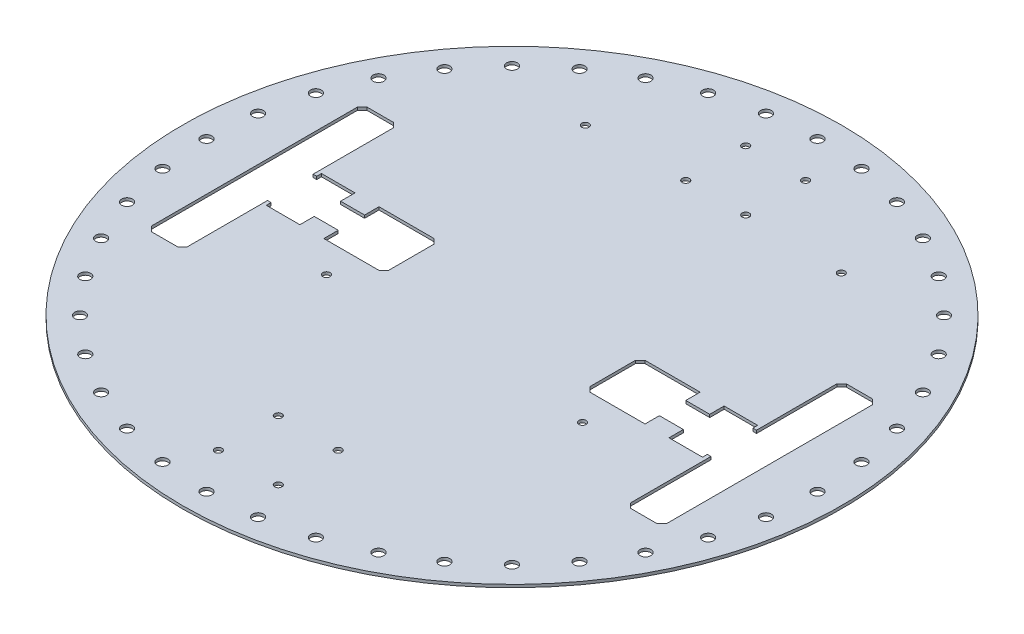
SolidWorks part; units mm, degrees
ref_plane "Front Plane" through (0, 0, 0) normal (0, 0, 1) x (1, 0, 0)
ref_plane "Top Plane" through (0, 0, 0) normal (0, 1, 0) x (1, 0, 0)
ref_plane "Right Plane" through (0, 0, 0) normal (1, 0, 0) x (0, 0, -1)
sketch "Sketch1" plane through (0, 0, 0) normal (0, 1, 0) x (1, 0, 0)
  circle A0 centre (0, 0) radius 137.5
  dimension "D1" = 275
extrude "Boss-Extrude1" add sketch "Sketch1" along normal blind 1.2
sketch "Sketch3" plane through (0, 1.2, 0) normal (0, 1, 0) x (1, 0, 0)
  line L0 (0, 127.4549) -> (0, 0) construction
  line L1 (0, 0) -> (19.9383, 125.8858) construction
  line L2 (39.3857, 121.2169) -> (0, 0) construction
  circle A0 centre (0, 127.4549) radius 2.25
  circle A2 centre (19.9383, 125.8858) radius 2.25
  circle A3 centre (39.3857, 121.2169) radius 2.25
  circle A4 centre (57.8633, 113.5632) radius 2.25
  circle A5 centre (74.9161, 103.1132) radius 2.25
  circle A6 centre (90.1243, 90.1243) radius 2.25
  circle A7 centre (103.1132, 74.9161) radius 2.25
  circle A8 centre (113.5632, 57.8633) radius 2.25
  circle A9 centre (121.2169, 39.3857) radius 2.25
  circle A10 centre (125.8858, 19.9383) radius 2.25
  circle A11 centre (127.4549, 0) radius 2.25
  circle A12 centre (125.8858, -19.9383) radius 2.25
  circle A13 centre (121.2169, -39.3857) radius 2.25
  circle A14 centre (113.5632, -57.8633) radius 2.25
  circle A15 centre (103.1132, -74.9161) radius 2.25
  circle A16 centre (90.1243, -90.1243) radius 2.25
  circle A17 centre (74.9161, -103.1132) radius 2.25
  circle A18 centre (57.8633, -113.5632) radius 2.25
  circle A19 centre (39.3857, -121.2169) radius 2.25
  circle A20 centre (19.9383, -125.8858) radius 2.25
  circle A21 centre (0, -127.4549) radius 2.25
  circle A22 centre (-19.9383, -125.8858) radius 2.25
  circle A23 centre (-39.3857, -121.2169) radius 2.25
  circle A24 centre (-57.8633, -113.5632) radius 2.25
  circle A25 centre (-74.9161, -103.1132) radius 2.25
  circle A26 centre (-90.1243, -90.1243) radius 2.25
  circle A27 centre (-103.1132, -74.9161) radius 2.25
  circle A28 centre (-113.5632, -57.8633) radius 2.25
  circle A29 centre (-121.2169, -39.3857) radius 2.25
  circle A30 centre (-125.8858, -19.9383) radius 2.25
  circle A31 centre (-127.4549, 0) radius 2.25
  circle A32 centre (-125.8858, 19.9383) radius 2.25
  circle A33 centre (-121.2169, 39.3857) radius 2.25
  circle A34 centre (-113.5632, 57.8633) radius 2.25
  circle A35 centre (-103.1132, 74.9161) radius 2.25
  circle A36 centre (-90.1243, 90.1243) radius 2.25
  circle A37 centre (-74.9161, 103.1132) radius 2.25
  circle A38 centre (-57.8633, 113.5632) radius 2.25
  circle A39 centre (-39.3857, 121.2169) radius 2.25
  circle A40 centre (-19.9383, 125.8858) radius 2.25
  dimension "D1" = 4.5
  dimension "D2" = 40
  dimension "D3" = 20
extrude "Cut-Extrude1" cut sketch "Sketch3" against normal through all
sketch "Sketch4" plane through (0, 1.2, 0) normal (0, 1, 0) x (1, 0, 0)
  line L0 (0, 137.5) -> (0, -137.5) construction
  line L1 (-137.5, 0) -> (137.5, 0) construction
  line L2 (-107.5, -43) -> (-107.5, 43)
  line L3 (-105.5, 45) -> (-94.5, 45)
  line L4 (-92.5, 43) -> (-92.5, 9.5)
  line L5 (-92.5, 9.5) -> (-91, 9.5)
  line L6 (-91, 9.5) -> (-91, 11.5)
  line L7 (-91, 11.5) -> (-77, 11.5)
  line L8 (-77, 11.5) -> (-77, 5.5)
  line L9 (-77, 5.5) -> (-67, 5.5)
  line L10 (-67, 5.5) -> (-67, 11.5)
  line L11 (-67, 11.5) -> (-44, 11.5)
  line L12 (-42, 9.5) -> (-42, -9.5)
  line L13 (-67, -11.5) -> (-44, -11.5)
  line L14 (-67, -5.5) -> (-67, -11.5)
  line L15 (-77, -5.5) -> (-67, -5.5)
  line L16 (-77, -11.5) -> (-77, -5.5)
  line L17 (-91, -11.5) -> (-77, -11.5)
  line L18 (-91, -9.5) -> (-91, -11.5)
  line L19 (-92.5, -9.5) -> (-91, -9.5)
  line L20 (-92.5, -43) -> (-92.5, -9.5)
  line L21 (-105.5, -45) -> (-94.5, -45)
  line L22 (-44, 11.5) -> (-42, 9.5)
  line L23 (-44, -11.5) -> (-42, -9.5)
  line L24 (-107.5, 43) -> (-105.5, 45)
  line L25 (-94.5, 45) -> (-92.5, 43)
  line L26 (-107.5, -43) -> (-105.5, -45)
  line L27 (-94.5, -45) -> (-92.5, -43)
  line L28 (94.5, -45) -> (92.5, -43)
  line L29 (107.5, -43) -> (105.5, -45)
  line L30 (94.5, 45) -> (92.5, 43)
  line L31 (107.5, 43) -> (105.5, 45)
  line L32 (44, -11.5) -> (42, -9.5)
  line L33 (44, 11.5) -> (42, 9.5)
  line L34 (105.5, -45) -> (94.5, -45)
  line L35 (92.5, -43) -> (92.5, -9.5)
  line L36 (92.5, -9.5) -> (91, -9.5)
  line L37 (91, -9.5) -> (91, -11.5)
  line L38 (91, -11.5) -> (77, -11.5)
  line L39 (77, -11.5) -> (77, -5.5)
  line L40 (77, -5.5) -> (67, -5.5)
  line L41 (67, -5.5) -> (67, -11.5)
  line L42 (67, -11.5) -> (44, -11.5)
  line L43 (42, 9.5) -> (42, -9.5)
  line L44 (67, 11.5) -> (44, 11.5)
  line L45 (67, 5.5) -> (67, 11.5)
  line L46 (77, 5.5) -> (67, 5.5)
  line L47 (77, 11.5) -> (77, 5.5)
  line L48 (91, 11.5) -> (77, 11.5)
  line L49 (91, 9.5) -> (91, 11.5)
  line L50 (92.5, 9.5) -> (91, 9.5)
  line L51 (92.5, 43) -> (92.5, 9.5)
  line L52 (105.5, 45) -> (94.5, 45)
  line L53 (107.5, -43) -> (107.5, 43)
  circle A2 centre (0, 0) radius 137.5 construction
  point P8 (-107.5, 45)
  point P9 (-42, -11.5)
  point P10 (-92.5, 45)
  point P18 (-42, 11.5)
  point P27 (-92.5, -45)
  point P28 (-107.5, -45)
  point P29 (-100, 0)
  point P39 (-100, 45)
  point P68 (100, 0)
  point P69 (107.5, -45)
  point P70 (92.5, -45)
  point P71 (42, 11.5)
  point P72 (92.5, 45)
  point P73 (42, -11.5)
  point P74 (107.5, 45)
  dimension "D1" = 90
  dimension "D2" = 15
  dimension "D3" = 100
  dimension "D4" = 1.5
  dimension "D5" = 2
  dimension "D6" = 14
  dimension "D7" = 23
  dimension "D8" = 6
  dimension "D9" = 10
  dimension "D10" = 35
extrude "Cut-Extrude2" cut sketch "Sketch4" against normal blind 1.2
sketch "Sketch5" plane through (0, 1.2, 0) normal (0, 1, 0) x (1, 0, 0)
  line L0 (0, 30) -> (0, 0) construction
  line L1 (-53.4, 84) -> (53.4, 84) construction
  line L2 (-53.4, 84) -> (-53.4, -24) construction
  line L3 (-53.4, -24) -> (53.4, -24) construction
  line L4 (53.4, 84) -> (53.4, -24) construction
  line L5 (-53.4, 84) -> (53.4, -24) construction
  line L6 (-53.4, -24) -> (53.4, 84) construction
  circle A0 centre (-53.4, 84) radius 1.5
  circle A1 centre (53.4, 84) radius 1.5
  circle A2 centre (53.4, -24) radius 1.5
  circle A3 centre (-53.4, -24) radius 1.5
  point P0 (0, 30)
  dimension "D3" = 3
  dimension "D1" = 106.8
  dimension "D2" = 108
  dimension "D4" = 30
extrude "Cut-Extrude3" cut sketch "Sketch5" against normal through all
sketch "Sketch6" plane through (0, 1.2, 0) normal (0, 1, 0) x (1, 0, 0)
  line L0 (-137.5, 0) -> (137.5, 0) construction
  line L1 (0, 137.5) -> (0, -137.5) construction
  line L2 (-12.5, -85) -> (12.5, -110) construction
  line L3 (-12.5, 110) -> (12.5, 110) construction
  line L4 (-12.5, 110) -> (-12.5, 85) construction
  line L5 (-12.5, 85) -> (12.5, 85) construction
  line L6 (12.5, 110) -> (12.5, 85) construction
  line L7 (-12.5, 110) -> (12.5, 85) construction
  line L8 (-12.5, 85) -> (12.5, 110) construction
  line L9 (-12.5, -110) -> (12.5, -85) construction
  line L10 (12.5, -110) -> (12.5, -85) construction
  line L11 (-12.5, -85) -> (12.5, -85) construction
  line L12 (-12.5, -110) -> (-12.5, -85) construction
  line L13 (-12.5, -110) -> (12.5, -110) construction
  circle A0 centre (0, 0) radius 137.5 construction
  circle A1 centre (-12.5, 110) radius 1.5
  circle A2 centre (12.5, 110) radius 1.5
  circle A3 centre (12.5, 85) radius 1.5
  circle A4 centre (-12.5, 85) radius 1.5
  circle A5 centre (-12.5, -85) radius 1.5
  circle A6 centre (12.5, -85) radius 1.5
  circle A7 centre (12.5, -110) radius 1.5
  circle A8 centre (-12.5, -110) radius 1.5
  point P7 (0, 97.5)
  point P24 (0, -97.5)
  dimension "D1" = 3
  dimension "D2" = 25
  dimension "D3" = 40
extrude "Cut-Extrude4" cut sketch "Sketch6" against normal through all
